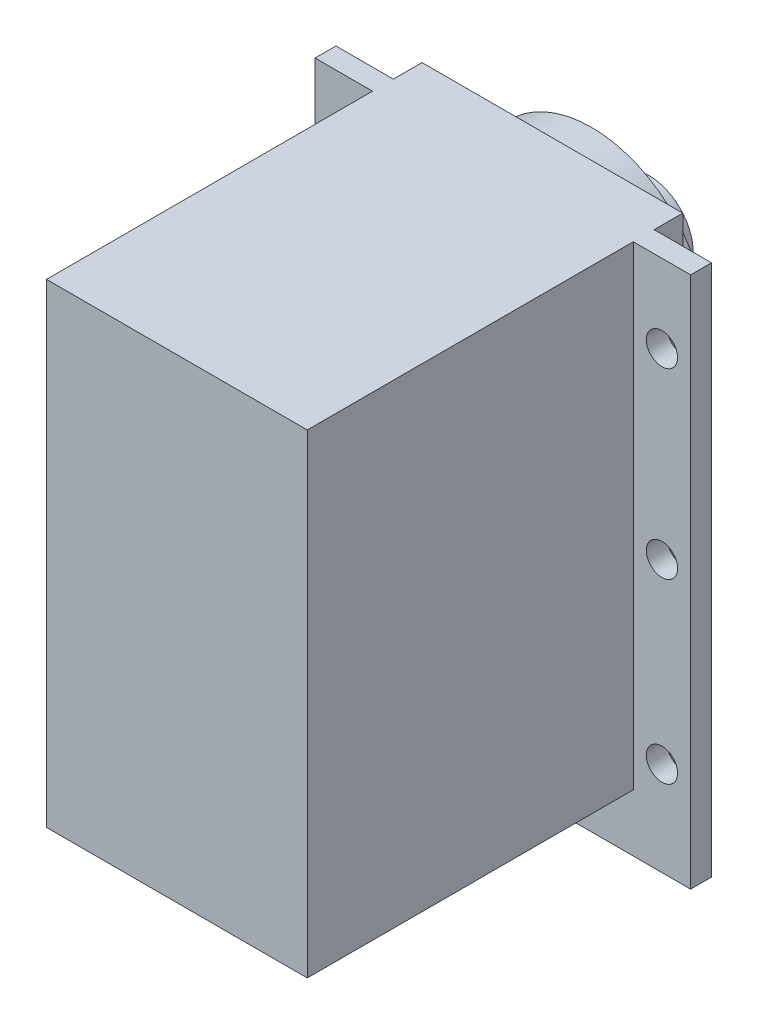
SolidWorks part; units mm, degrees
ref_plane "Front Plane" through (0, 0, 0) normal (0, 0, 1) x (1, 0, 0)
ref_plane "Top Plane" through (0, 0, 0) normal (0, 1, 0) x (1, 0, 0)
ref_plane "Right Plane" through (0, 0, 0) normal (1, 0, 0) x (0, 0, -1)
sketch "Sketch1" plane through (0, 0, 0) normal (0, 0, 1) x (1, 0, 0)
  line L1 (-12.5, -22.75) -> (12.5, -22.75)
  line L2 (-12.5, -22.75) -> (-12.5, 22.75)
  line L3 (-12.5, 22.75) -> (12.5, 22.75)
  line L4 (12.5, -22.75) -> (12.5, 22.75)
  line L5 (-12.5, -22.75) -> (12.5, 22.75) construction
  line L6 (-12.5, 22.75) -> (12.5, -22.75) construction
  point P0 (0, 0)
  dimension "D1" = 25
  dimension "D2" = 45.5
extrude "Boss-Extrude1" add sketch "Sketch1" along normal blind 36
sketch "Sketch2" plane through (0, 0, 0) normal (0, 0, -1) x (-1, 0, 0)
  line L0 (-12.5, 22.75) -> (12.5, 22.75) construction
  line L1 (-18, 22.75) -> (18, 22.75)
  line L2 (-18, 22.75) -> (-18, -28.25)
  line L3 (-18, -28.25) -> (18, -28.25)
  line L4 (18, 22.75) -> (18, -28.25)
  line L5 (-12.5, -22.75) -> (-12.5, 22.75) construction
  line L6 (12.5, 22.75) -> (12.5, -22.75) construction
  line L7 (12.5, -22.75) -> (-12.5, -22.75) construction
  line L8 (-18, 20.9329) -> (-12.5, 20.9329) construction
  line L9 (12.5, 18.8932) -> (18, 18.8932) construction
  line L10 (2.0803, -28.25) -> (2.0803, -22.75) construction
  circle A0 centre (-15.25, 15.25) radius 1.5
  circle A1 centre (-15.25, -2.25) radius 1.5
  circle A2 centre (-15.25, -19.25) radius 1.5
  circle A3 centre (-7.5, -25.5) radius 1.5
  circle A4 centre (7.5, -25.5) radius 1.5
  circle A5 centre (15.25, -19.25) radius 1.5
  circle A6 centre (15.25, -2.25) radius 1.5
  circle A7 centre (15.25, 15.25) radius 1.5
  point P28 (2.0803, -25.5)
  point P29 (-15.25, 20.9329)
  point P32 (15.25, 18.8932)
  point P37 (0, 0)
  dimension "D4" = 3
  dimension "D5" = 7.5
  dimension "D1" = 5.5
  dimension "D2" = 5.5
  dimension "D3" = 5.5
  dimension "D6" = 25
  dimension "D7" = 42
  dimension "D8" = 5
  dimension "D9" = 5
extrude "Boss-Extrude2" add sketch "Sketch2" against normal blind 2 from offset 2.75 offset against normal yes
sketch "Sketch3" plane through (0, 0, 0) normal (0, 0, -1) x (-1, 0, 0)
  line L0 (-12.5, 22.75) -> (12.5, 22.75) construction
  circle A0 centre (0, 10.75) radius 11
  point P4 (0, 0)
  point P5 (0, 22.75)
  dimension "D1" = 22
  dimension "D2" = 12
extrude "Boss-Extrude3" add sketch "Sketch3" along normal blind 3.75
sketch "Sketch4" plane through (0, 0, -3.75) normal (0, 0, -1) x (-1, 0, 0)
  circle A0 centre (0, 18.75) radius 1.5
  circle A1 centre (0, 10.75) radius 11 construction
  circle A2 centre (-5.6569, 16.4069) radius 1.5
  circle A3 centre (-8, 10.75) radius 1.5
  circle A4 centre (-5.6569, 5.0931) radius 1.5
  circle A5 centre (0, 2.75) radius 1.5
  circle A6 centre (5.6569, 5.0931) radius 1.5
  circle A7 centre (8, 10.75) radius 1.5
  circle A8 centre (5.6569, 16.4069) radius 1.5
  point P21 (0, 10.75)
  dimension "D1" = 3
  dimension "D2" = 8
  dimension "D3" = 8
extrude "Cut-Extrude1" cut sketch "Sketch4" against normal blind 3.75
sketch "Sketch5" plane through (0, 0, -3.75) normal (0, 0, -1) x (-1, 0, 0)
  circle A0 centre (0, 10.75) radius 4.25
  dimension "D1" = 8.5
extrude "Boss-Extrude4" add sketch "Sketch5" along normal blind 5.5
